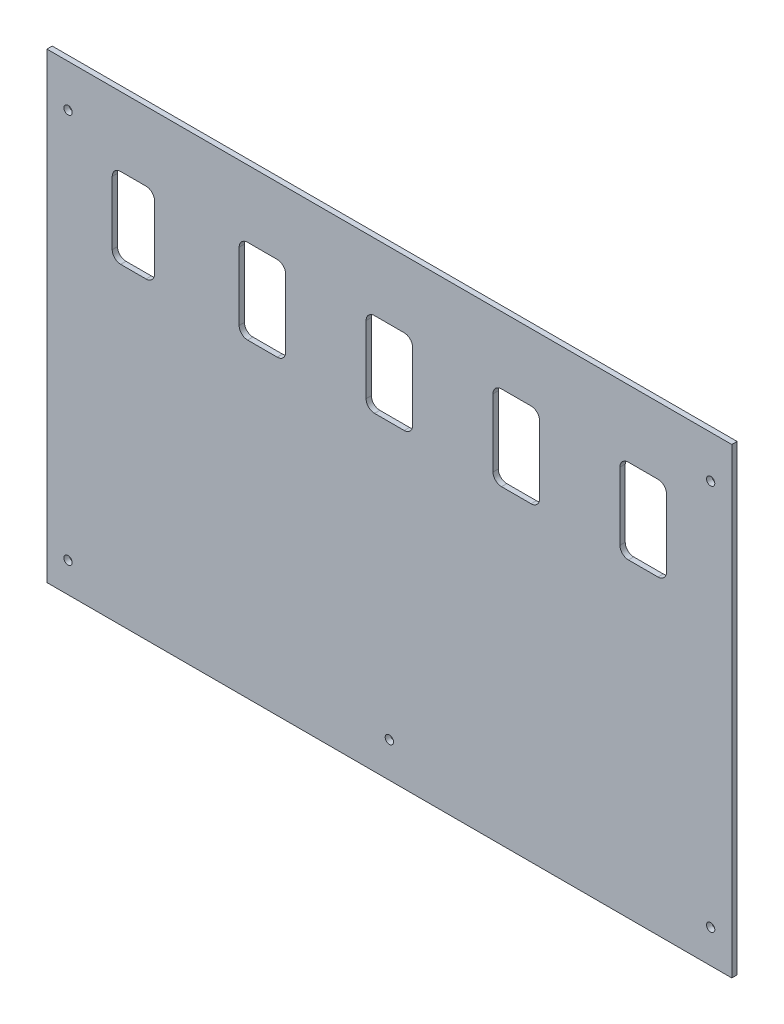
SolidWorks part; units mm, degrees
material "ABS PC"
ref_plane "Front Plane" through (0, 0, 0) normal (0, 0, 1) x (1, 0, 0)
ref_plane "Top Plane" through (0, 0, 0) normal (0, 1, 0) x (1, 0, 0)
ref_plane "Right Plane" through (0, 0, 0) normal (1, 0, 0) x (0, 0, -1)
sketch "Sketch1" plane through (0, 0, 0) normal (0, 0, 1) x (1, 0, 0)
  line L1 (-205.5812, -138.684) -> (205.5812, -138.684)
  line L2 (-205.5812, -138.684) -> (-205.5812, 138.684)
  line L3 (-205.5812, 138.684) -> (205.5812, 138.684)
  line L4 (205.5812, -138.684) -> (205.5812, 138.684)
  line L5 (0, 138.684) -> (0, -138.684) construction
  line L6 (-205.5812, 0) -> (205.5813, 0) construction
  point P0 (0, 0)
  point P4 (-137.0013, 0)
  point P5 (137.0013, 0)
  point P6 (0, 97.0788)
  point P7 (0, -97.0788)
  dimension "Width" = 277.368
  dimension "Break" = 68.58
  dimension "D2" = 68.58
  dimension "D1" = 41.6052
  dimension "D3" = 41.6052
  dimension "D4" = 411.1625
sketch "Sketch2" plane through (0, 0, 0) normal (1, 0, 0) x (0, 0, -1)
  line L0 (-1.5875, -138.684) -> (1.5875, -138.684)
  dimension "Thickness" = 3.175
sketch "Sketch3" plane through (0, 0, 0) normal (0, 0, 1) x (1, 0, 0)
  line L0 (-205.5812, -138.684) -> (-205.5812, 138.684) construction
  line L1 (-205.5812, -138.684) -> (205.5812, -138.684) construction
  line L2 (205.5812, -138.684) -> (205.5812, 138.684) construction
  line L3 (-205.5812, 138.684) -> (205.5812, 138.684) construction
  line L4 (-205.5812, -138.684) -> (-205.5812, 138.684)
  line L5 (-205.5812, -138.684) -> (205.5812, -138.684)
  line L6 (205.5812, -138.684) -> (205.5812, 138.684)
  line L7 (-205.5812, 138.684) -> (205.5812, 138.684)
extrude "Boss-Extrude1" add sketch "Sketch3" along normal mid plane 3.175
sketch "Sketch4" plane through (0, 0, 1.5875) normal (0, 0, 1) x (1, 0, 0)
  line L0 (-227.6475, 73.0327) -> (-161.29, 73.0327) construction
  line L1 (-82.55, 73.0327) -> (-82.55, 98.4327) construction
  line L2 (-82.55, 98.4327) -> (-90.17, 98.4327) construction
  line L3 (-161.29, 73.0327) -> (-161.29, 97.1627) construction
  line L6 (-227.6475, -105.791) -> (-227.6475, 52.959) construction
  line L7 (-227.6475, -115.316) -> (-227.6475, 138.684) construction
  line L8 (-161.29, 73.0327) -> (-82.55, 73.0327) construction
  line L9 (-82.55, 73.0327) -> (-6.35, 73.0327) construction
  line L10 (-6.35, 73.0327) -> (69.85, 73.0327) construction
  line L11 (69.85, 73.0327) -> (146.05, 73.0327) construction
  line L12 (-82.55, 73.0327) -> (-82.55, 47.6327) construction
  line L13 (-82.55, 47.6327) -> (-62.23, 47.6327) construction
  line L16 (-161.29, 97.1627) -> (-166.37, 97.1627) construction
  line L17 (-161.29, 73.0327) -> (-161.29, 48.9027) construction
  line L18 (-161.29, 48.9027) -> (-140.97, 48.9027) construction
  line L19 (-6.35, 73.0327) -> (-6.35, 98.4327) construction
  line L24 (-6.35, 98.4327) -> (-13.97, 98.4327) construction
  line L25 (-6.35, 73.0327) -> (-6.35, 47.6327) construction
  line L26 (-6.35, 47.6327) -> (13.97, 47.6327) construction
  line L27 (69.85, 73.0327) -> (69.85, 98.4327) construction
  line L28 (-8.89, 98.4327) -> (8.89, 98.4327)
  line L29 (-13.97, 93.3527) -> (-13.97, 52.7127)
  line L30 (-8.89, 47.6327) -> (8.89, 47.6327)
  line L31 (13.97, 93.3527) -> (13.97, 52.7127)
  line L32 (69.85, 98.4327) -> (62.23, 98.4327) construction
  line L33 (69.85, 73.0327) -> (69.85, 47.6327) construction
  line L34 (69.85, 47.6327) -> (90.17, 47.6327) construction
  line L35 (146.05, 73.0327) -> (146.05, 98.4327) construction
  line L36 (67.31, 98.4327) -> (85.09, 98.4327)
  line L37 (62.23, 93.3527) -> (62.23, 52.7127)
  line L38 (67.31, 47.6327) -> (85.09, 47.6327)
  line L39 (90.17, 93.3527) -> (90.17, 52.7127)
  line L40 (146.05, 98.4327) -> (138.43, 98.4327) construction
  line L41 (146.05, 73.0327) -> (146.05, 47.6327) construction
  line L42 (146.05, 47.6327) -> (166.37, 47.6327) construction
  line L43 (-205.5812, 138.684) -> (-205.5812, 73.0327) construction
  line L44 (143.51, 98.4327) -> (161.29, 98.4327)
  line L45 (138.43, 93.3527) -> (138.43, 52.7127)
  line L46 (143.51, 47.6327) -> (161.29, 47.6327)
  line L47 (166.37, 93.3527) -> (166.37, 52.7127)
  line L48 (-85.09, 98.4327) -> (-67.31, 98.4327)
  line L49 (-90.17, 93.3527) -> (-90.17, 52.7127)
  line L50 (-85.09, 47.6327) -> (-67.31, 47.6327)
  line L51 (-62.23, 93.3527) -> (-62.23, 52.7127)
  line L53 (-161.29, 97.1627) -> (-146.05, 97.1627)
  line L54 (-166.37, 92.0827) -> (-166.37, 53.9827)
  line L55 (-161.29, 48.9027) -> (-146.05, 48.9027)
  line L56 (-140.97, 92.0827) -> (-140.97, 53.9827)
  arc A0 (138.43, 52.7127) -> (143.51, 47.6327) centre (143.51, 52.7127) ccw
  arc A1 (166.37, 52.7127) -> (161.29, 47.6327) centre (161.29, 52.7127) cw
  arc A2 (161.29, 98.4327) -> (166.37, 93.3527) centre (161.29, 93.3527) cw
  arc A3 (138.43, 93.3527) -> (143.51, 98.4327) centre (143.51, 93.3527) cw
  arc A4 (62.23, 52.7127) -> (67.31, 47.6327) centre (67.31, 52.7127) ccw
  arc A5 (90.17, 52.7127) -> (85.09, 47.6327) centre (85.09, 52.7127) cw
  arc A6 (85.09, 98.4327) -> (90.17, 93.3527) centre (85.09, 93.3527) cw
  arc A7 (67.31, 98.4327) -> (62.23, 93.3527) centre (67.31, 93.3527) ccw
  arc A8 (-13.97, 52.7127) -> (-8.89, 47.6327) centre (-8.89, 52.7127) ccw
  arc A9 (13.97, 52.7127) -> (8.89, 47.6327) centre (8.89, 52.7127) cw
  arc A10 (8.89, 98.4327) -> (13.97, 93.3527) centre (8.89, 93.3527) cw
  arc A11 (-8.89, 98.4327) -> (-13.97, 93.3527) centre (-8.89, 93.3527) ccw
  arc A19 (-90.17, 52.7127) -> (-85.09, 47.6327) centre (-85.09, 52.7127) ccw
  arc A20 (-62.23, 52.7127) -> (-67.31, 47.6327) centre (-67.31, 52.7127) cw
  arc A21 (-67.31, 98.4327) -> (-62.23, 93.3527) centre (-67.31, 93.3527) cw
  arc A22 (-85.09, 98.4327) -> (-90.17, 93.3527) centre (-85.09, 93.3527) ccw
  arc A23 (-166.37, 53.9827) -> (-161.29, 48.9027) centre (-161.29, 53.9827) ccw
  arc A24 (-146.05, 48.9027) -> (-140.97, 53.9827) centre (-146.05, 53.9827) ccw
  arc A25 (-146.05, 97.1627) -> (-140.97, 92.0827) centre (-146.05, 92.0827) cw
  arc A26 (-161.29, 97.1627) -> (-166.37, 92.0827) centre (-161.29, 92.0827) ccw
  point P16 (-76.2, 98.4327)
  point P17 (-90.17, 73.0327)
  point P18 (-13.97, 73.0327)
  point P95 (62.23, 73.0327)
  point P96 (138.43, 73.0327)
  point P97 (0, 98.4327)
  point P98 (76.2, 98.4327)
  point P99 (152.4, 98.4327)
  dimension "D1" = 5.08
  dimension "D2" = 5.08
  dimension "D5" = 5.08
  dimension "D9" = 27.94
  dimension "D10" = 27.94
  dimension "D11" = 27.94
  dimension "D12" = 27.94
  dimension "D3" = 76.2
  dimension "D4" = 76.2
  dimension "D6" = 152.4
  dimension "D7" = 65.6513
extrude "Cut-Extrude1" cut sketch "Sketch4" against normal blind 25.4 contours L53 A26 L54 A23 L55 A24 L56 A25 | A22 L48 A21 L51 A20 L50 A19 L49 | L29 A8 L30 A9 L31 A10 L28 A11 | L37 A4 L38 A5 L39 A6 L36 A7 | A3 L44 A2 L47 A1 L46 A0 L45 region at (-153.67, 73.0327, 1.5875)
hole_wizard "#10 Clearance Hole1" positions "Sketch5" profile "Sketch6" hole size "#10" standard "ANSI Inch" end condition through all
sketch "Sketch5" plane through (0, 0, 1.5875) normal (0, 0, 1) x (1, 0, 0)
  point P6 (192.8812, 113.284)
  point P8 (-192.8812, -120.7642)
  point P10 (192.8812, -118.6475)
  point P12 (-192.8812, 113.284)
sketch "Sketch6" plane through (192.8812, 113.284, 1.5875) normal (1, 0, 0) x (0, -1, 0)
  line L0 (0, 0) -> (0, 3.175)
  line L1 (0, 3.175) -> (2.4892, 3.175)
  line L2 (2.4892, 3.175) -> (2.4892, 0)
  line L5 (2.4892, 0) -> (0, 0)
  line L11 (0, -6.35) -> (0, 107.95) construction
  dimension "Thru Hole Dia." = 4.9784
  dimension "Thru Hole Depth" = 3.175
hole_wizard "#10 Clearance Hole2" positions "Sketch7" profile "Sketch8" hole size "#10" standard "ANSI Inch" end condition through all
sketch "Sketch7" plane through (0, 0, 1.5875) normal (0, 0, 1) x (1, 0, 0)
  point P0 (0, -117.5325)
sketch "Sketch8" plane through (0, -117.5325, 1.5875) normal (1, 0, 0) x (0, -1, 0)
  line L0 (0, 0) -> (0, 3.175)
  line L1 (0, 3.175) -> (2.4892, 3.175)
  line L2 (2.4892, 3.175) -> (2.4892, 0)
  line L5 (2.4892, 0) -> (0, 0)
  line L11 (0, -6.35) -> (0, 107.95) construction
  dimension "Thru Hole Dia." = 4.9784
  dimension "Thru Hole Depth" = 3.175
equation "\"D1@Boss-Extrude1\" = \"Thickness@Sketch2\""
equation "\"D2@Sketch1\" = \"Break@Sketch1\""
equation "\"D1@Sketch1\"=\"Width@Sketch1\"*0.15"
equation "\"D3@Sketch1\"=\"D1@Sketch1\""
equation "\"SlotWidth\"= 1.1in"
equation "\"D9@Sketch4\"=\"SlotWidth\""
equation "\"D10@Sketch4\"=\"SlotWidth\""
equation "\"D11@Sketch4\"=\"SlotWidth\""
equation "\"D12@Sketch4\"=\"SlotWidth\""
